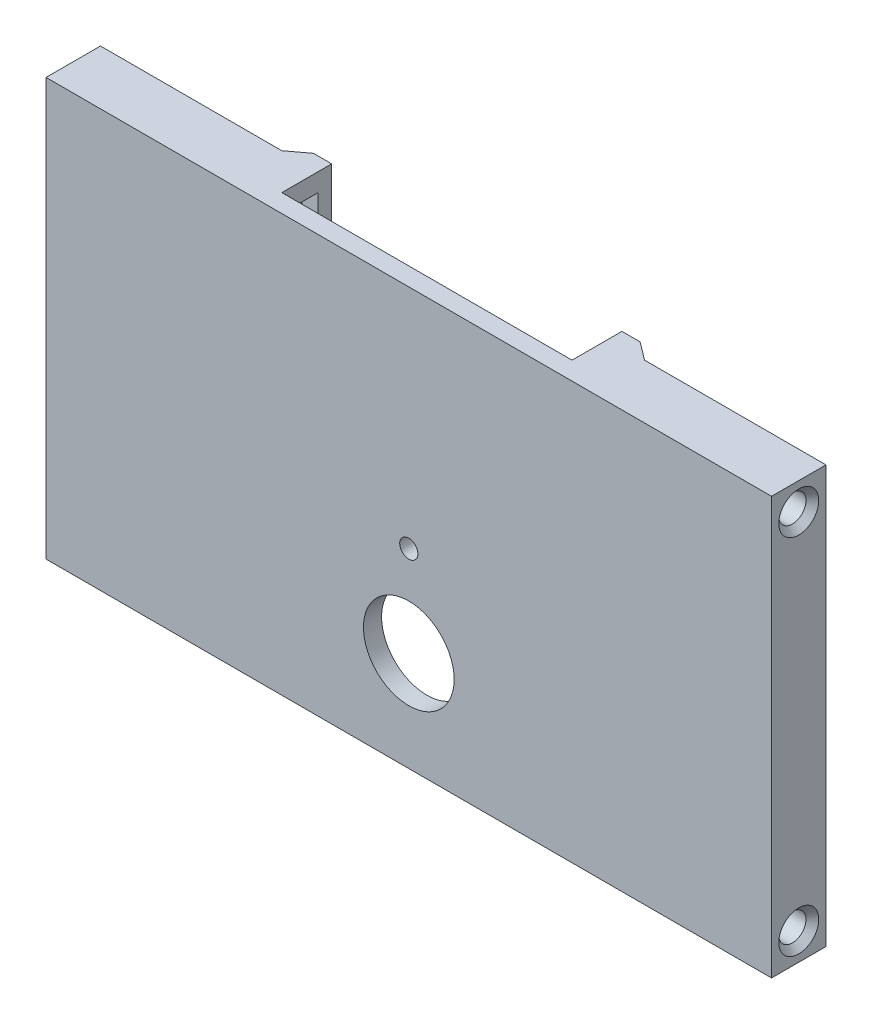
SolidWorks part; units mm, degrees
material "ABS"
ref_plane "Ebene vorne" through (0, 0, 0) normal (0, 0, 1) x (1, 0, 0)
ref_plane "Ebene oben" through (0, 0, 0) normal (0, 1, 0) x (1, 0, 0)
ref_plane "Ebene rechts" through (0, 0, 0) normal (1, 0, 0) x (0, 0, -1)
sketch "Skizze1" plane through (0, 0, 0) normal (0, 0, 1) x (1, 0, 0)
  line L0 (0, 50.7625) -> (0, -50.1476) construction
  line L1 (-61.9688, 0) -> (71.1622, 0) construction
  line L2 (-40, -23) -> (-40, 23)
  line L3 (-40, 23) -> (40, 23)
  line L4 (40, -23) -> (40, 23)
  line L5 (-40, -23) -> (40, -23)
  circle A0 centre (0, -12) radius 5
  circle A1 centre (0, -2) radius 1
  point P9 (0, 23)
  point P10 (0, -23)
  point P12 (40, 0)
  point P13 (-40, 0)
  dimension "D3" = 12
  dimension "D4" = 10
  dimension "D5" = 2
  dimension "D6" = 2
  dimension "D1" = 80
  dimension "D2" = 46
extrude "Aufsatz-Linear austragen1" add sketch "Skizze1" along normal blind 3 and the other way blind 3
hole_wizard "Ø3.0 (3) Durchmesser Bohrung1" positions "Skizze3" profile "Skizze2" hole size "Ø3.0" standard "ANSI Metrisch"
sketch "Skizze3" plane through (40, 0, 0) normal (1, 0, 0) x (0, 0, -1)
  line L0 (0, -57.6805) -> (0, 49.3664) construction
  line L3 (-29.0599, 0) -> (25.5739, 0) construction
  point P0 (0, -20)
  point P14 (0, 20)
  dimension "D1" = 40
sketch "Skizze2" plane through (40, -20, 0) normal (0, 1, 0) x (0, 0, -1)
  line L0 (0, 0) -> (0, 12.9013)
  line L1 (0, 12.9013) -> (1.5, 12)
  line L2 (1.5, 12) -> (1.5, 0)
  line L5 (1.5, 0) -> (0, 0)
  line L10 (0, 12.9013) -> (-1.5, 12) construction
  line L11 (0, -6.35) -> (0, 107.95) construction
  dimension "Bohrerdurchmesser" = 3
  dimension "Bohrungstiefe" = 12
  dimension "Spitzenwinkel" = 118
mirror "Spiegeln1" about plane through (0, 0, 0) normal (1, 0, 0) of "Ø3.0 (3) Durchmesser Bohrung1"
sketch "Skizze4" plane through (0, 0, -3) normal (0, 0, 1) x (1, 0, 0)
  line L0 (-60.4279, 0) -> (54.1706, 0) construction
  line L1 (0, 30.4132) -> (0, -30.8408) construction
  line L2 (-16, -23) -> (-16, 23)
  line L3 (-16, 23) -> (16, 23)
  line L4 (16, -23) -> (16, 23)
  line L5 (-16, -23) -> (16, -23)
  line L6 (40, 23) -> (-40, 23) construction
  point P9 (0, 23)
  point P10 (0, -23)
  point P12 (16, 0)
  point P13 (-16, 0)
  dimension "D2" = 32
extrude "Schnitt-Linear austragen1" cut sketch "Skizze4" along normal blind 4
sketch "Skizze6" plane through (0, 0, -3) normal (0, 0, -1) x (-1, 0, 0)
  line L0 (47.8486, 0) -> (-47.4384, 0) construction
  line L1 (0, -32.6631) -> (0, 31.7076) construction
  line L2 (37, 15) -> (37, -15)
  line L3 (35, -17) -> (22, -17)
  line L4 (20, -15) -> (20, 15)
  line L5 (35, 17) -> (22, 17)
  line L6 (-35, 17) -> (-22, 17)
  line L7 (-20, -15) -> (-20, 15)
  line L8 (-35, -17) -> (-22, -17)
  line L9 (-37, 15) -> (-37, -15)
  line L10 (40, 23) -> (40, -23) construction
  line L13 (16, 23) -> (16, -23) construction
  arc A0 (20, -15) -> (22, -17) centre (22, -15) ccw
  arc A1 (35, -17) -> (37, -15) centre (35, -15) ccw
  arc A2 (35, 17) -> (37, 15) centre (35, 15) cw
  arc A3 (20, 15) -> (22, 17) centre (22, 15) cw
  arc A4 (-20, 15) -> (-22, 17) centre (-22, 15) ccw
  arc A5 (-35, 17) -> (-37, 15) centre (-35, 15) ccw
  arc A6 (-35, -17) -> (-37, -15) centre (-35, -15) cw
  arc A7 (-20, -15) -> (-22, -17) centre (-22, -15) cw
  point P7 (37, 0)
  point P19 (20, 0)
  point P31 (-20, 0)
  point P32 (-37, 0)
  dimension "D1" = 2
  dimension "D2" = 3
  dimension "D3" = 34
  dimension "D4" = 4
extrude "Schnitt-Linear austragen3" cut sketch "Skizze6" against normal offset from surface (4.5 mm away) 1.5 up to face at (5, -12, 3)
sketch "Skizze9" plane through (0, 0, -3) normal (0, 0, -1) x (-1, 0, 0)
  line L0 (0, 38.9694) -> (0, -35.923) construction
  line L1 (-49.298, 0) -> (44.3683, 0) construction
  line L2 (-17.75, -23) -> (-17.75, 21)
  line L3 (-16, -23) -> (-40, -23) construction
  line L4 (-17.75, 21) -> (17.75, 21)
  line L5 (-17.75, -23) -> (17.75, -23)
  line L6 (17.75, -23) -> (17.75, 21)
  line L7 (-16, 23) -> (16, 23) construction
  point P12 (0, -23)
  point P13 (0, 21)
  dimension "D1" = 35.5
  dimension "D2" = 2
extrude "Schnitt-Linear austragen5" cut sketch "Skizze9" against normal offset from surface (2 mm away) 2 up to face at (1, -2, 1)
sketch "Skizze10" plane through (0, 23, 0) normal (0, 1, 0) x (1, 0, 0)
  line L0 (-16, 3) -> (-16, 4.5)
  line L1 (-16, 4.5) -> (-18, 4.5)
  line L2 (-18, 4.5) -> (-20, 3)
  line L3 (-16, 3) -> (-40, 3) construction
  line L4 (-20, 3) -> (-16, 3)
  line L5 (0, 27.1298) -> (0, -16.3879) construction
  line L6 (20, 3) -> (16, 3)
  line L7 (18, 4.5) -> (20, 3)
  line L8 (16, 4.5) -> (18, 4.5)
  line L9 (16, 3) -> (16, 4.5)
  dimension "D1" = 1.5
  dimension "D2" = 2
  dimension "D3" = 4
extrude "Aufsatz-Linear austragen2" add sketch "Skizze10" against normal blind 34
chamfer "Fase1" distance 0.7 angle 45 4 edges at (-40, -20, 1.5) (-40, 20, 1.5) (40, 20, -1.5) (40, -20, -1.5)
ref_axis "Achse1" through (-44, 0, 0) along (1, 0, 0)
ref_axis "Achse2" through (0, 0, -4.875) along (0, 0, 1)
ref_axis "Achse3" through (0, 25.3, 0) along (0, -1, 0)
